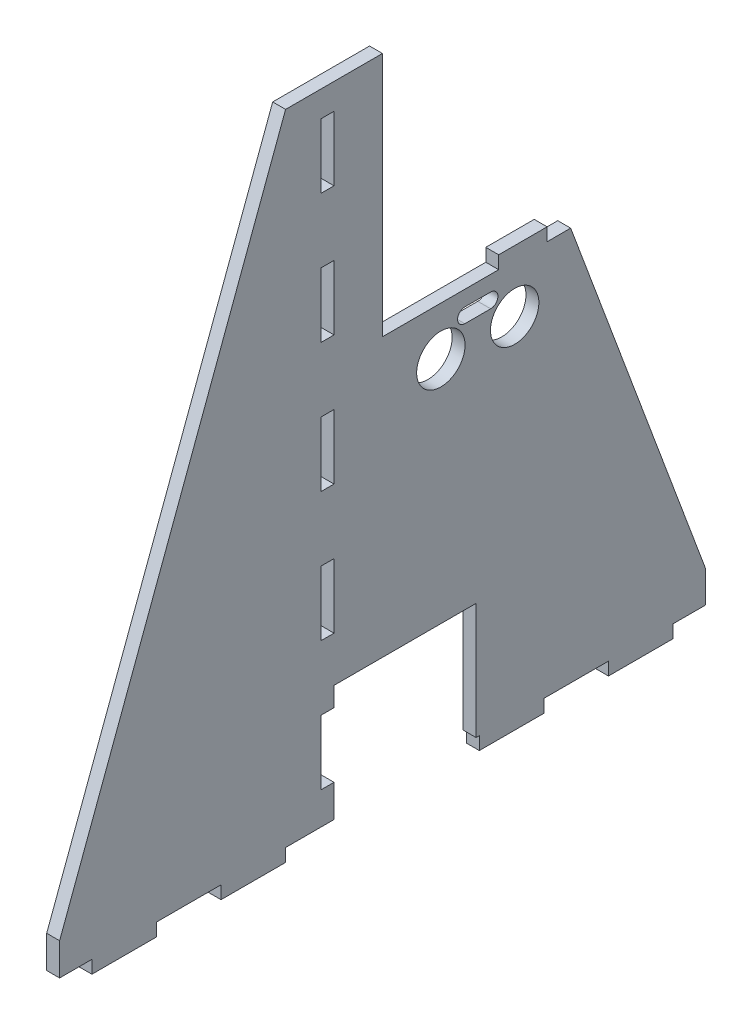
SolidWorks part; units mm, degrees
ref_plane "Přední rovina" through (0, 0, 0) normal (0, 0, 1) x (1, 0, 0)
ref_plane "Horní rovina" through (0, 0, 0) normal (0, 1, 0) x (1, 0, 0)
ref_plane "Pravá rovina" through (0, 0, 0) normal (1, 0, 0) x (0, 0, -1)
sketch "Skica1" plane through (0, 0, 0) normal (1, 0, 0) x (0, 0, -1)
  line L0 (0, 0) -> (0, 200)
  line L1 (-100, 0) -> (100, 0)
  line L2 (-100, 0) -> (-100, 202)
  line L3 (-100, 202) -> (100, 202)
  line L4 (100, 0) -> (100, 202)
  line L5 (-90, 0) -> (-70, 0)
  line L6 (-90, 0) -> (-90, 4)
  line L7 (-90, 4) -> (-70, 4)
  line L8 (-70, 0) -> (-70, 4)
  line L9 (-50, 0) -> (-30, 0)
  line L10 (-50, 0) -> (-50, 4)
  line L11 (-50, 4) -> (-30, 4)
  line L12 (-30, 0) -> (-30, 4)
  line L13 (-10, 0) -> (10, 0)
  line L17 (50, 4) -> (30, 4)
  line L18 (30, 0) -> (30, 4)
  line L19 (50, 0) -> (30, 0)
  line L20 (50, 0) -> (50, 4)
  line L21 (90, 4) -> (70, 4)
  line L22 (70, 0) -> (70, 4)
  line L23 (90, 0) -> (70, 0)
  line L24 (90, 0) -> (90, 4)
  line L25 (-8.5, 37) -> (0, 37)
  line L26 (0, 200) -> (0, 202)
  line L27 (-15, 14) -> (-19, 14)
  line L28 (-15, 14) -> (-15, 34)
  line L29 (-15, 34) -> (-19, 34)
  line L30 (-19, 14) -> (-19, 34)
  line L31 (-15, 54) -> (-19, 54)
  line L32 (-15, 54) -> (-15, 74)
  line L33 (-15, 74) -> (-19, 74)
  line L34 (-19, 54) -> (-19, 74)
  line L35 (-15, 94) -> (-19, 94)
  line L36 (-15, 94) -> (-15, 114)
  line L37 (-15, 114) -> (-19, 114)
  line L38 (-19, 94) -> (-19, 114)
  line L39 (-15, 134) -> (-19, 134)
  line L40 (-15, 134) -> (-15, 154)
  line L41 (-15, 154) -> (-19, 154)
  line L42 (-19, 134) -> (-19, 154)
  line L43 (-15, 174) -> (-19, 174)
  line L44 (-15, 174) -> (-15, 194)
  line L45 (-15, 194) -> (-19, 194)
  line L46 (-19, 174) -> (-19, 194)
  line L47 (-30, 202) -> (-100, 14)
  line L48 (100, 14) -> (30, 202)
  line L49 (58.2979, 126) -> (0, 126)
  line L50 (25.5223, 119) -> (33.5223, 119) construction
  line L51 (36, 126) -> (51, 126)
  line L52 (36, 126) -> (36, 130)
  line L53 (36, 130) -> (51, 130)
  line L54 (51, 126) -> (51, 130)
  line L55 (25.5223, 121.25) -> (33.5223, 121.25)
  line L56 (25.5223, 116.75) -> (33.5223, 116.75)
  line L57 (-100, 4) -> (-90, 4)
  line L58 (-70, 4) -> (-50, 4)
  line L59 (-30, 4) -> (-15, 4)
  line L60 (30, 4) -> (29, 4)
  line L61 (50, 4) -> (70, 4)
  line L62 (90, 4) -> (100, 4)
  line L64 (-15, 40) -> (29, 40)
  line L65 (-15, 40) -> (-15, 0)
  line L66 (-15, 0) -> (29, 0)
  line L67 (29, 40) -> (29, 0)
  line L68 (-15, 40) -> (29, 0) construction
  line L69 (-15, 0) -> (29, 40) construction
  circle A3 centre (18.0923, 111) radius 7.5
  circle A4 centre (40.9523, 111) radius 7.5
  arc A5 (25.5223, 121.25) -> (25.5223, 116.75) centre (25.5223, 119) ccw
  arc A6 (33.5223, 116.75) -> (33.5223, 121.25) centre (33.5223, 119) ccw
  point P20 (-70, 2)
  point P21 (-80, 4)
  point P56 (-17, 174)
  point P57 (-30, 202)
  point P59 (30, 202)
  point P76 (29.5223, 119)
  point P82 (7, 20)
  dimension "D31" = 15
  dimension "D33" = 8
  dimension "D37" = 8
  dimension "D7" = 10
  dimension "D1" = 200
  dimension "D2" = 100
  dimension "D3" = 202
  dimension "D5" = 0
  dimension "D6" = 20
  dimension "D8" = 20
  dimension "D9" = 20
  dimension "D10" = 4
  dimension "D11" = 0
  dimension "D12" = 0
  dimension "D14" = 8.5
  dimension "D16" = 37
  dimension "D17" = 10
  dimension "D18" = 20
  dimension "D19" = 20
  dimension "D20" = 20
  dimension "D21" = 20
  dimension "D22" = 20
  dimension "D23" = 20
  dimension "D24" = 20
  dimension "D25" = 20
  dimension "D26" = 20
  dimension "D27" = 4
  dimension "D28" = 15
  dimension "D29" = 30
  dimension "D30" = 22.86
  dimension "D32" = 74
  dimension "D34" = 36
  dimension "D35" = 15
  dimension "D36" = 73.2979
  dimension "D38" = 11.43
  dimension "D39" = 8
  dimension "D40" = 4.5
  dimension "D41" = 4
  dimension "D42" = 40
  dimension "D43" = 44
extrude "Přidat vysunutím1" add sketch "Skica1" along normal blind 4 contours L64 L67 L60 L17 L61 L21 L62 L4 L48 L49 L0 A6 L56 A5 L55 A4 A3 | L65 L64 L0 L26 L3 L47 L2 L57 L7 L58 L11 L59 L27 L30 L29 L31 L34 L33 L32 L35 L38 L37 L36 L39 L42 L41 L40 L43 L46 L45 L44 | L49 L54 L53 L52 | L1 L8 L7 L6 | L1 L12 L11 L10 | L1 L20 L17 L18 | L1 L24 L21 L22 region at (0, 87.0608, 38.655) region at (0, 61.5019, -45.3726) region at (0, 2, 40) region at (0, 2, -40) region at (0, 128, -43.5) region at (0, 2, 80) region at (0, 2, -80)
